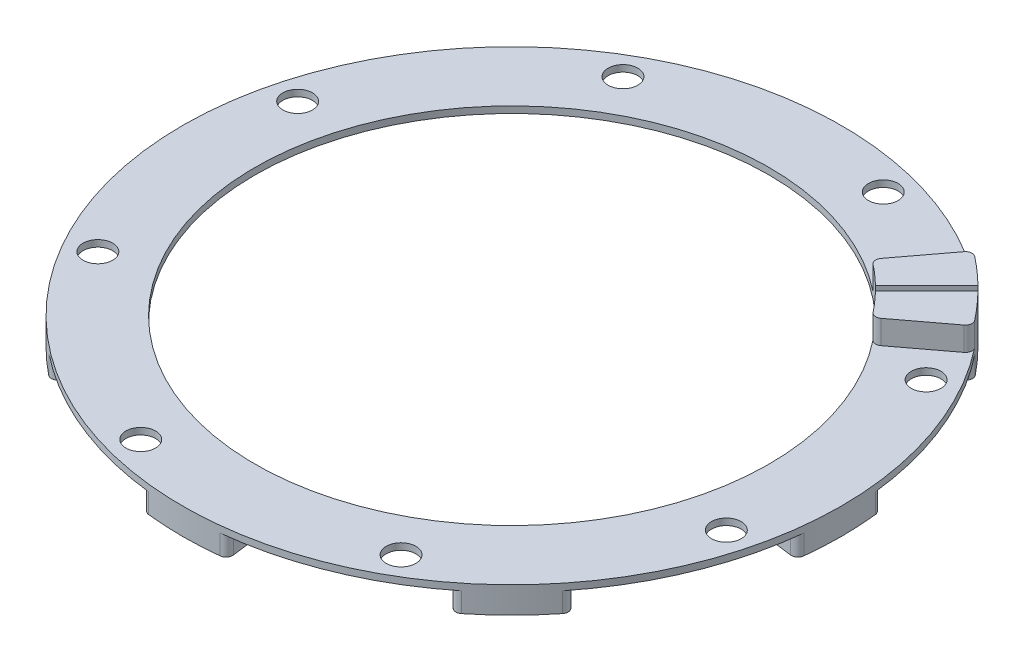
SolidWorks part; units mm, degrees
material "AISI 1045 钢，冷拔"
ref_plane "前视基准面" through (0, 0, 0) normal (0, 0, 1) x (1, 0, 0)
ref_plane "上视基准面" through (0, 0, 0) normal (0, 1, 0) x (1, 0, 0)
ref_plane "右视基准面" through (0, 0, 0) normal (1, 0, 0) x (0, 0, -1)
sketch "草图1" plane through (0, 0, 0) normal (0, 1, 0) x (1, 0, 0)
  circle A0 centre (0, 0) radius 50
  circle A1 centre (0, 0) radius 39
  dimension "D1" = 100
  dimension "D2" = 78
extrude "凸台-拉伸1" add sketch "草图1" along normal blind 1
sketch "草图2" plane through (0, 1, 0) normal (0, 1, 0) x (1, 0, 0)
  line L0 (0, 0) -> (0, 46) construction
  line L1 (0, 0) -> (11.9057, 44.4326) construction
  line L2 (0, 0) -> (-23, 39.8372) construction
  circle A0 centre (0, 0) radius 46 construction
  circle A1 centre (11.9057, 44.4326) radius 2.25
  circle A2 centre (-23, 39.8372) radius 2.25
  circle A3 centre (39.8372, 23) radius 2.25
  circle A4 centre (44.4326, -11.9057) radius 2.25
  circle A5 centre (23, -39.8372) radius 2.25
  circle A6 centre (-11.9057, -44.4326) radius 2.25
  circle A7 centre (-39.8372, -23) radius 2.25
  circle A8 centre (-44.4326, 11.9057) radius 2.25
  point P23 (0, 0)
  dimension "D1" = 92
  dimension "D2" = 15
  dimension "D4" = 4.5
  dimension "D5" = 4.5
  dimension "D3" = 30
  dimension "D6" = 4
extrude "切除-拉伸1" cut sketch "草图2" against normal blind 2
sketch "草图3" plane through (0, 0, 0) normal (0, -1, 0) x (1, 0, 0)
  line L0 (0, 0) -> (0, 50) construction
  line L1 (0, 0) -> (6.4398, 49.5836)
  line L2 (0, 0) -> (-6.4398, 49.5836)
  circle A0 centre (0, 0) radius 50 construction
  circle A1 centre (0, 0) radius 45.6
  circle M13 centre (0, 0) radius 50
  dimension "D1" = 91.2
  dimension "D2" = 7.4
  dimension "D3" = 7.4
extrude "凸台-拉伸2" add sketch "草图3" along normal blind 3 contours A1 L0 L2 M13 | L0 A1 L1 M13
fillet "圆角1" radius 1 2 edges at (5.8731, -1.5, 45.2202) (-5.8731, -1.5, 45.2202)
pattern_circular "阵列(圆周)1" count 8 over 360 about axis through (0, 0, 0) along (0, 1, 0) of "凸台-拉伸2"
sketch "草图4" plane through (0, 1, 0) normal (0, 1, 0) x (1, 0, 0)
  line L0 (0, 0) -> (39.8372, 23) construction
  line L1 (0, 0) -> (35.3553, 35.3553) construction
  line L2 (0, 0) -> (39.9318, 30.0908)
  line L3 (0, 0) -> (30.0908, 39.9318)
  circle A0 centre (0, 0) radius 39 construction
  circle A1 centre (0, 0) radius 50
  circle A2 centre (0, 0) radius 50
  circle A3 centre (0, 0) radius 39
  circle M14 centre (0, 0) radius 50
  circle M15 centre (0, 0) radius 39
  dimension "D2" = 15
  dimension "D3" = 8
  dimension "D4" = 8
  dimension "D1" = 0
extrude "凸台-拉伸3" add sketch "草图4" along normal blind 3.6 contours L3 L2 M15 M14
fillet "圆角2" radius 1 4 edges at (39.9318, 2.8, -30.0908) (31.1468, 2.8, -23.4708) (23.4708, 2.8, -31.1468) (30.0908, 2.8, -39.9318)
fillet "圆角3" radius 1 30 edges at (5.8731, -1.5, -45.2202) (-5.8731, -1.5, -45.2202) (-6.4398, -1.5, -49.5836) (6.4398, -1.5, -49.5836) (-27.8226, -1.5, -36.1284) (-36.1284, -1.5, -27.8226) (-39.6145, -1.5, -30.5073) (-30.5073, -1.5, -39.6145) (-45.2202, -1.5, -5.8731) (-45.2202, -1.5, 5.8731) (-49.5836, -1.5, 6.4398) (-49.5836, -1.5, -6.4398) (-36.1284, -1.5, 27.8226) (-27.8226, -1.5, 36.1284) (-30.5073, -1.5, 39.6145) (-39.6145, -1.5, 30.5073) (6.4398, -1.5, 49.5836) (-6.4398, -1.5, 49.5836) (27.8226, -1.5, 36.1284) (36.1284, -1.5, 27.8226) (39.6145, -1.5, 30.5073) (30.5073, -1.5, 39.6145) (45.2202, -1.5, 5.8731) (45.2202, -1.5, -5.8731) (49.5836, -1.5, -6.4398) (49.5836, -1.5, 6.4398) (36.1284, -1.5, -27.8226) (27.8226, -1.5, -36.1284) (30.5073, -1.5, -39.6145) (39.6145, -1.5, -30.5073)
sketch "草图5" plane through (0, 4.6, 0) normal (0, 1, 0) x (1, 0, 0)
  line L0 (0, 0) -> (35.3553, 35.3553) construction
  line L1 (36.0543, 36.7614) -> (36.7614, 36.0543)
  line L2 (36.7614, 36.0543) -> (25.1102, 24.4031)
  line L3 (25.1102, 24.4031) -> (24.4031, 25.1102)
  line L4 (24.4031, 25.1102) -> (36.0543, 36.7614)
  arc A0 (39.3094, 30.8994) -> (30.8994, 39.3094) centre (0, 0) ccw construction
  dimension "D1" = 0.5
  dimension "D2" = 1
extrude "切除-拉伸2" cut sketch "草图5" against normal blind 1
